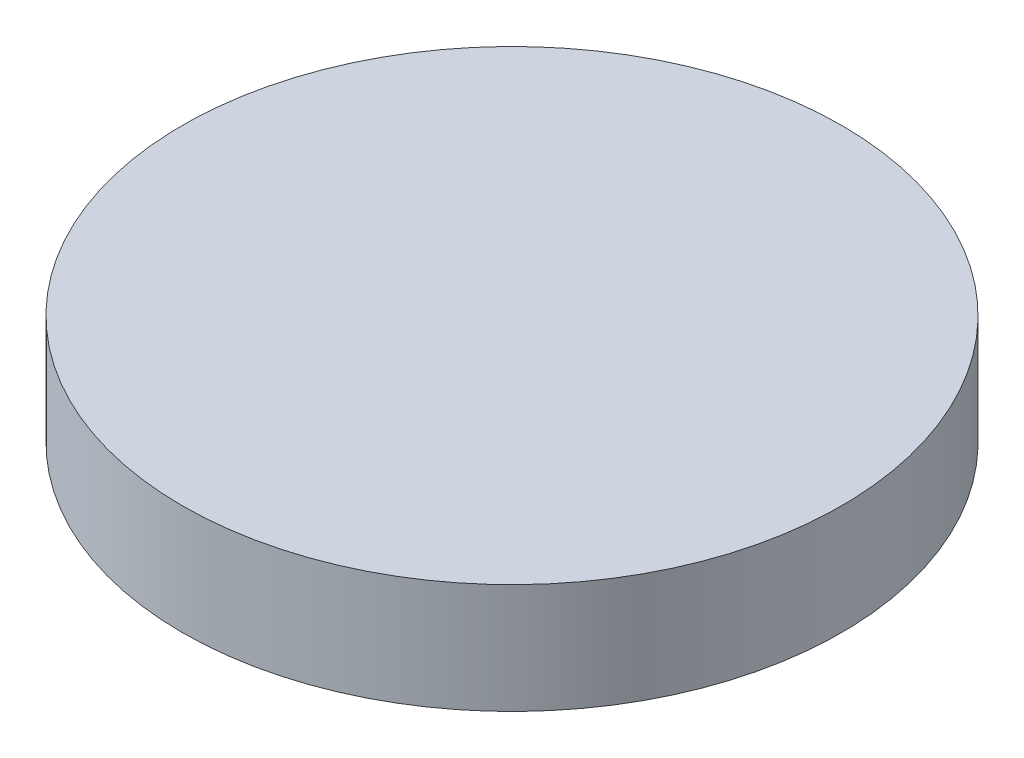
SolidWorks part; units mm, degrees
ref_plane "Front Plane" through (0, 0, 0) normal (0, 0, 1) x (1, 0, 0)
ref_plane "Top Plane" through (0, 0, 0) normal (0, 1, 0) x (1, 0, 0)
ref_plane "Right Plane" through (0, 0, 0) normal (1, 0, 0) x (0, 0, -1)
sketch "Sketch1" plane through (0, 0, 0) normal (0, 1, 0) x (1, 0, 0)
  circle A0 centre (-47.7088, -19.327) radius 19.05
  dimension "D1" = 38.1
extrude "Boss-Extrude1" add sketch "Sketch1" along normal blind 6.35
